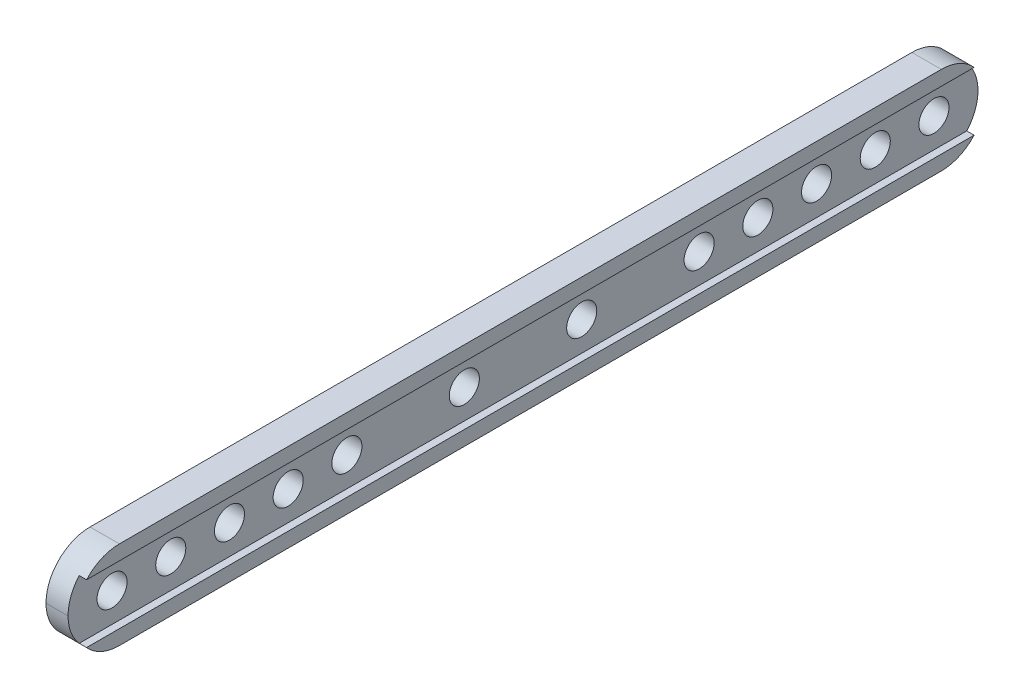
SolidWorks part; units mm, degrees
ref_plane "Front Plane" through (0, 0, 0) normal (0, 0, 1) x (1, 0, 0)
ref_plane "Top Plane" through (0, 0, 0) normal (0, 1, 0) x (1, 0, 0)
ref_plane "Right Plane" through (0, 0, 0) normal (1, 0, 0) x (0, 0, -1)
sketch "Sketch1" plane through (0, 0, 0) normal (0, 0, 1) x (1, 0, 0)
  line L0 (3, 6) -> (0, 6) construction
  line L1 (0, 0) -> (4, 0)
  line L2 (0, 0) -> (0, 12)
  line L3 (0, 12) -> (4, 12)
  line L4 (4, 0) -> (4, 2)
  line L5 (4, 10) -> (3, 10)
  line L7 (4, 2) -> (3, 2)
  line L8 (3, 10) -> (3, 2)
  line L9 (4, 10) -> (4, 12)
  dimension "D1" = 4
  dimension "D2" = 12
  dimension "D3" = 8
  dimension "D4" = 1
extrude "Boss-Extrude1" add sketch "Sketch1" against normal blind 124
ref_plane "Plane1" through (0, 0, -62) normal (0, 0, 1) x (1, 0, 0)
fillet "Fillet1" radius 6 4 edges at (2, 12, 0) (2, 0, 0) (2, 0, -124) (2, 12, -124)
sketch "Sketch2" plane through (0, 0, 0) normal (-1, 0, 0) x (0, 0, 1)
  circle A0 centre (-118, 6) radius 2.05
  dimension "D1" = 4.1
extrude "Cut-Extrude1" cut sketch "Sketch2" against normal through all
pattern_linear "LPattern1" count 7 spacing 8 along (0, 0, 1) skipping (5, 0) of "Cut-Extrude1"
mirror "Mirror1" about plane through (0, 0, -62) normal (0, 0, 1) of "LPattern1", "Cut-Extrude1"
